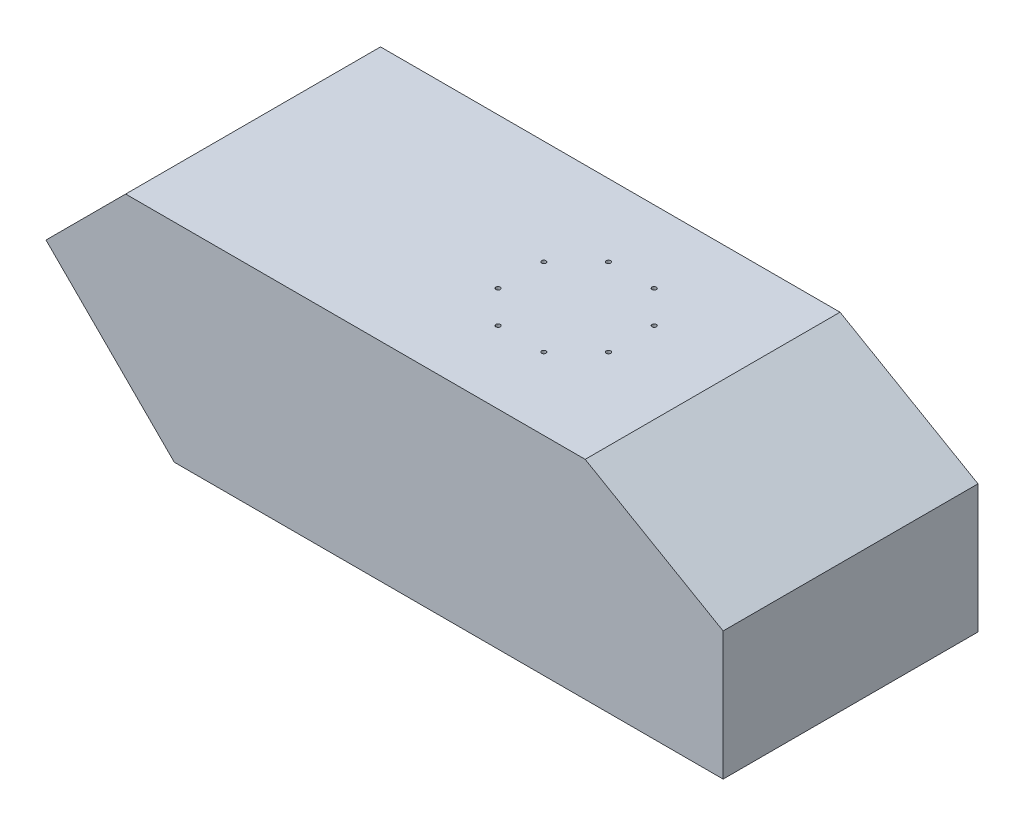
SolidWorks part; units mm, degrees
ref_plane "Front" through (0, 0, 0) normal (0, 0, 1) x (1, 0, 0)
ref_plane "Top" through (0, 0, 0) normal (0, 1, 0) x (1, 0, 0)
ref_plane "Right" through (0, 0, 0) normal (1, 0, 0) x (0, 0, -1)
sketch "Croquis3" plane through (0, 0, 0) normal (0, 0, 1) x (1, 0, 0)
  line L0 (-344.53, -161.11) -> (344.53, -161.11)
  line L2 (344.53, -161.11) -> (344.53, 0)
  line L3 (344.53, 0) -> (171.3249, 100)
  line L4 (171.3249, 100) -> (-405.64, 100)
  line L5 (-405.64, 100) -> (-505.64, 0)
  line L6 (-505.64, 0) -> (-344.53, -161.11)
  line L7 (0, -55) -> (0, 55) construction
  line L8 (55, 0) -> (-55, 0) construction
  point P11 (0, -161.11)
  dimension "D1" = 850.17
  dimension "D2" = 261.11
  dimension "D3" = 45
  dimension "D4" = 30
  dimension "D5" = 45
  dimension "D6" = 100
extrude "Saliente-Extruir2" add sketch "Croquis3" along normal mid plane 320
hole_wizard "Taladro de margen para M51" positions "Croquis6" profile "Croquis8" hole size "M5" standard "Ansi Metric"
sketch "Croquis6" plane through (0, 100, 0) normal (0, 1, 0) x (1, 0, 0)
  line L7 (28.7013, 69.291) -> (0, 0) construction
  line L10 (0, -143.6105) -> (0, 143.6105) construction
  line L11 (0, 0) -> (-28.7013, -69.291) construction
  point P34 (28.7013, 69.291)
  point P51 (69.291, 28.7013)
  point P52 (69.291, -28.7013)
  point P53 (28.7013, -69.291)
  point P54 (-28.7013, -69.291)
  point P55 (-69.291, -28.7013)
  point P56 (-69.291, 28.7013)
  point P57 (-28.7013, 69.291)
  dimension "D1" = 75
  dimension "D2" = 22.5
  dimension "D3" = 8
sketch "Croquis8" plane through (28.7013, 100, -69.291) normal (1, 0, 0) x (0, 0, 1)
  line L0 (0, 0) -> (0, 23.6524)
  line L1 (0, 23.6524) -> (2.75, 22)
  line L2 (2.75, 22) -> (2.75, 0)
  line L5 (2.75, 0) -> (0, 0)
  line L10 (0, 23.6524) -> (-2.75, 22) construction
  line L11 (0, -6.35) -> (0, 107.95) construction
  dimension "Diámetro de taladro" = 5.5
  dimension "Profundidad de taladro" = 22
  dimension "Ángulo de perforador" = 118
